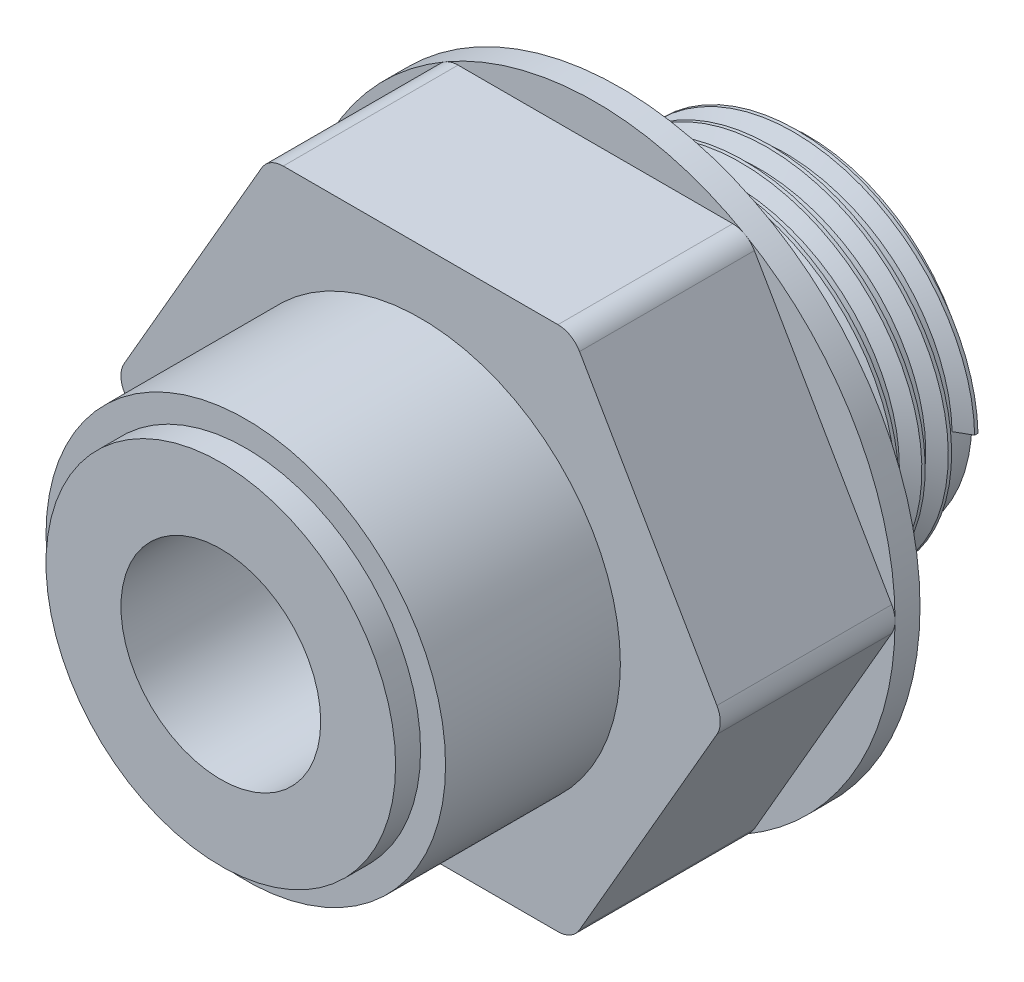
SolidWorks part; units mm, degrees
ref_plane "Front Plane" through (0, 0, 0) normal (0, 0, 1) x (1, 0, 0)
ref_plane "Top Plane" through (0, 0, 0) normal (0, 1, 0) x (1, 0, 0)
ref_plane "Right Plane" through (0, 0, 0) normal (1, 0, 0) x (0, 0, -1)
sketch "Sketch2" plane through (0, 0, 0) normal (1, 0, 0) x (0, 0, -1)
  line L0 (-17.6659, 0) -> (22.2536, 0) construction
  line L1 (0, 3.25) -> (23.5, 3.25)
  line L2 (23.5, 3.25) -> (23.5, 6.5785)
  line L3 (23.5, 6.5785) -> (16, 6.5785)
  line L4 (16, 6.5785) -> (16, 12)
  line L5 (16, 12) -> (8, 12)
  line L8 (8, 12) -> (8, 8)
  line L9 (8, 8) -> (0, 8)
  line L10 (0, 8) -> (0, 3.25)
  dimension "D1" = 23.5
  dimension "D2" = 16
  dimension "D3" = 8
  dimension "D4" = 12
  dimension "D5" = 3.25
  dimension "D8" = 6.5785
  dimension "D9" = 8
revolve "Revolve1" add sketch "Sketch2" angle 360 about L0
thread "Thread1" pitch 1.0583 method extrude profile "Thread Profile1" start angle 0, offset 0, length 0, pitch 1.0583, diameter 13.157
ref_plane "Plane1" through (6.5785, 0, -23.5) normal (0, -1, 0) x (1, 0, 0)
sketch "Thread Profile1" plane through (6.5785, 0, -23.5) normal (0, -1, 0) x (1, 0, 0)
  line L0 (0, 0) -> (0, 1.0583) construction
  line L1 (0, 0) -> (0.5728, 0.3307)
  line L2 (0.5728, 0.3307) -> (0.5728, 0.463)
  line L3 (0.5728, 0.463) -> (0, 0.7937)
  line L4 (0.5728, 0.3969) -> (0, 0.3969) construction
  line L11 (0, 0) -> (0, 0.7937)
  point P2 (0, 0)
  dimension "Pitch" = 1.0583
  dimension "Profile_Angle" = 60
  dimension "Profile_Land" = 0.1323
  dimension "Profile_Height" = 0.5728
sketch "Sketch6" plane through (0, 0, 0) normal (0, 0, 1) x (1, 0, 0)
  circle A0 centre (0, 0) radius 7
  circle A1 centre (0, 0) radius 8 construction
  dimension "D1" = 1
extrude "Cut-Extrude1" cut sketch "Sketch6" against normal blind 1 flip side to cut
sketch "Sketch8" plane through (0, 0, -8) normal (0, 0, 1) x (1, 0, 0)
  line L0 (-5.5, 10.5263) -> (5.5, 10.5263)
  line L1 (6.366, 10.0263) -> (11.866, 0.5)
  line L2 (11.866, -0.5) -> (6.366, -10.0263)
  line L3 (5.5, -10.5263) -> (-5.5, -10.5263)
  line L4 (-6.366, -10.0263) -> (-11.866, -0.5)
  line L5 (-11.866, 0.5) -> (-6.366, 10.0263)
  arc A0 (5.5, 10.5263) -> (6.366, 10.0263) centre (5.5, 9.5263) cw
  arc A1 (11.866, 0.5) -> (11.866, -0.5) centre (11, 0) cw
  arc A2 (6.366, -10.0263) -> (5.5, -10.5263) centre (5.5, -9.5263) cw
  arc A3 (-5.5, -10.5263) -> (-6.366, -10.0263) centre (-5.5, -9.5263) cw
  arc A4 (-11.866, -0.5) -> (-11.866, 0.5) centre (-11, 0) cw
  arc A5 (-5.5, 10.5263) -> (-6.366, 10.0263) centre (-5.5, 9.5263) ccw
  circle A6 centre (0, 0) radius 12 construction
  dimension "D1" = 1
extrude "Cut-Extrude3" cut sketch "Sketch8" against normal blind 7 flip side to cut
sketch "Sketch9" plane through (0, 0, 0) normal (0, 0, 1) x (1, 0, 0)
  circle A0 centre (0, 0) radius 4
  dimension "D1" = 8
extrude "Cut-Extrude4" cut sketch "Sketch9" against normal up to surface (16 mm away) up to face at (12, 0, -16)
